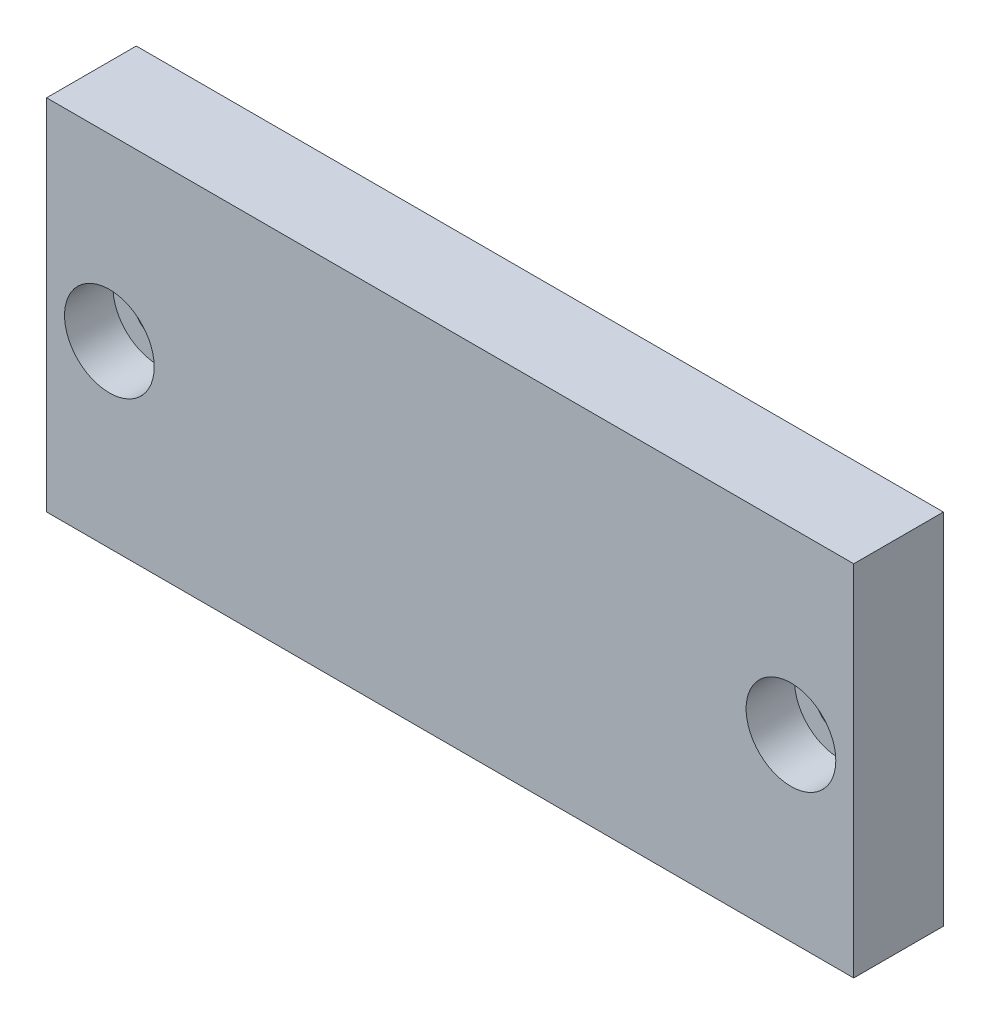
SolidWorks part; units mm, degrees
ref_plane "Front Plane" through (0, 0, 0) normal (0, 0, 1) x (1, 0, 0)
ref_plane "Top Plane" through (0, 0, 0) normal (0, 1, 0) x (1, 0, 0)
ref_plane "Right Plane" through (0, 0, 0) normal (1, 0, 0) x (0, 0, -1)
sketch "Sketch1" plane through (0, 0, 0) normal (0, 0, 1) x (1, 0, 0)
  line L1 (-46.8167, 18.4566) -> (43.1833, 18.4566)
  line L2 (-46.8167, 18.4566) -> (-46.8167, -21.5434)
  line L3 (-46.8167, -21.5434) -> (43.1833, -21.5434)
  line L4 (43.1833, 18.4566) -> (43.1833, -21.5434)
  dimension "D1" = 40
  dimension "D2" = 90
extrude "Boss-Extrude1" add sketch "Sketch1" along normal blind 10
sketch "Sketch2" plane through (0, 0, 10) normal (0, 0, 1) x (1, 0, 0)
  line L0 (43.1833, 18.4566) -> (-46.8167, 18.4566) construction
  line L1 (-46.8167, 18.4566) -> (-46.8167, -21.5434) construction
  line L2 (43.1833, -21.5434) -> (43.1833, 18.4566) construction
  circle A0 centre (-39.8167, -1.5434) radius 5
  circle A1 centre (36.1833, -1.5434) radius 5
  circle A2 centre (-39.8167, -1.5434) radius 2.75
  circle A3 centre (36.1833, -1.5434) radius 2.75
  dimension "D1" = 10
  dimension "D2" = 10
  dimension "D3" = 20
  dimension "D7" = 5.5
  dimension "D8" = 5.5
  dimension "D4" = 20
  dimension "D5" = 7
  dimension "D6" = 7
extrude "Cut-Extrude1" cut sketch "Sketch2" against normal blind 33 and the other way blind 67 contours A2
extrude "Cut-Extrude2" cut sketch "Sketch2<4>" against normal blind 35 and the other way blind 56 contours A3
sketch "Sketch2<4>" plane through (0, 0, 10) normal (0, 0, 1) x (1, 0, 0) same geometry as "Sketch2"
extrude "Cut-Extrude3" cut sketch "Sketch2<5>" against normal blind 5.4 contours A0
sketch "Sketch2<5>" plane through (0, 0, 10) normal (0, 0, 1) x (1, 0, 0) same geometry as "Sketch2"
extrude "Cut-Extrude4" cut sketch "Sketch2<6>" against normal blind 5.4 contours A1
sketch "Sketch2<6>" plane through (0, 0, 10) normal (0, 0, 1) x (1, 0, 0) same geometry as "Sketch2"
